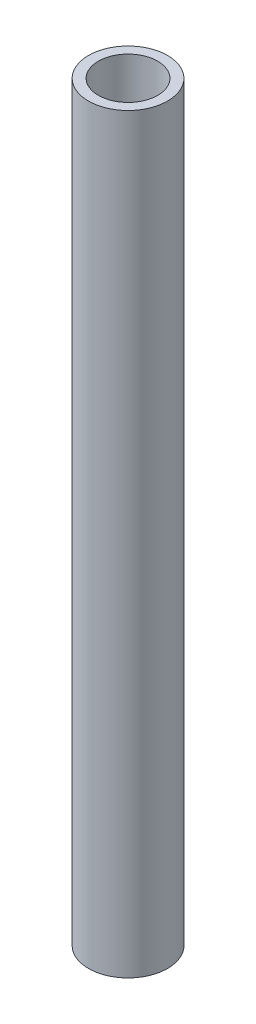
SolidWorks part; units mm, degrees
ref_plane "Front Plane" through (0, 0, 0) normal (0, 0, 1) x (1, 0, 0)
ref_plane "Top Plane" through (0, 0, 0) normal (0, 1, 0) x (1, 0, 0)
ref_plane "Right Plane" through (0, 0, 0) normal (1, 0, 0) x (0, 0, -1)
sketch "Sketch1" plane through (0, 0, 0) normal (0, 1, 0) x (1, 0, 0)
  circle A0 centre (-391.1817, 212.7433) radius 12.7
  circle A1 centre (-391.1817, 212.7433) radius 9.525
  dimension "D1" = 19.05
  dimension "D2" = 25.4
extrude "Boss-Extrude2" add sketch "Sketch1" along normal blind 241.3
